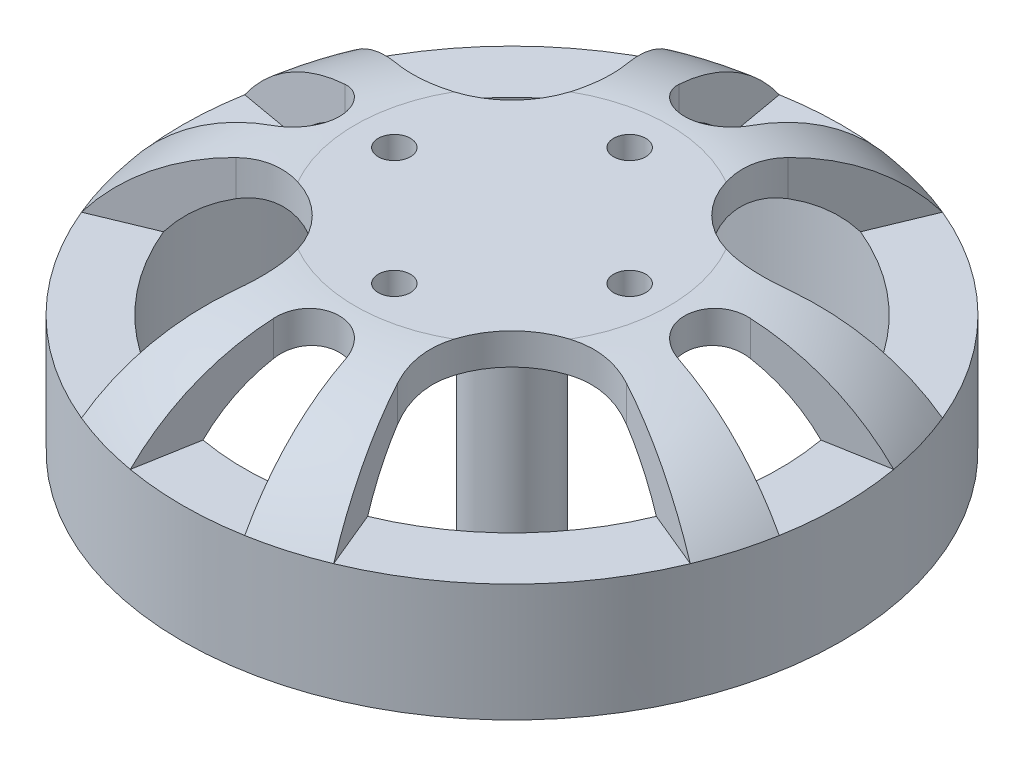
SolidWorks part; units mm, degrees
ref_plane "Front Plane" through (0, 0, 0) normal (0, 0, 1) x (1, 0, 0)
ref_plane "Top Plane" through (0, 0, 0) normal (0, 1, 0) x (1, 0, 0)
ref_plane "Right Plane" through (0, 0, 0) normal (1, 0, 0) x (0, 0, -1)
sketch "Sketch2" plane through (0, 0, 0) normal (0, 0, 1) x (1, 0, 0)
  line L0 (0, 0) -> (0, 19)
  line L1 (-21, 13.5) -> (-21, 6)
  line L2 (0, 19) -> (-10, 19)
  line L3 (0, 9.5) -> (-21, 9.5) construction
  line L4 (-21, 6) -> (-17, 6)
  line L5 (-17, 6) -> (-17, 13.5)
  line L6 (0, 0) -> (-2.5, 0)
  line L7 (-2.5, 0) -> (-2.5, 17)
  line L8 (-2.5, 17) -> (-10, 17)
  arc A0 (-10, 19) -> (-21, 13.5) centre (-10, 5.25) ccw
  arc A1 (-10, 17) -> (-17, 13.5) centre (-10, 8.25) ccw
  dimension "D1" = 21
  dimension "D2" = 19
  dimension "D3" = 7.5
  dimension "D4" = 10
  dimension "D5" = 4
  dimension "D6" = 2.5
  dimension "D7" = 2
  dimension "D8" = 4
revolve "Revolve2" add sketch "Sketch2" angle 360 about L0
hole_wizard "M2.5x0.45 Tapped Hole1" positions "Sketch4" profile "Sketch3" tap size "M2.5x0.45" standard "ANSI Metric" end condition up to next
sketch "Sketch4" plane through (0, 19, 0) normal (0, 1, 0) x (1, 0, 0)
  line L0 (0, 7.5) -> (0, -7.5) construction
  line L3 (-7.5, 0) -> (7.5, 0) construction
  point P0 (7.5, 0)
  point P2 (0, 7.5)
  point P4 (-7.5, 0)
  point P6 (0, -7.5)
  dimension "D1" = 15
sketch "Sketch3" plane through (7.5, 19, 0) normal (1, 0, 0) x (0, 0, 1)
  line L0 (0, 0) -> (0, 2)
  line L1 (0, 2) -> (1.025, 2)
  line L2 (1.025, 2) -> (1.025, 0)
  line L5 (1.025, 0) -> (0, 0)
  line L11 (0, -6.35) -> (0, 107.95) construction
  dimension "Thread Major Dia." = 2.05
  dimension "Thru Tap Drill Depth" = 2
sketch "Sketch6" plane through (0, 19, 0) normal (0, 1, 0) x (1, 0, 0)
  line L0 (0, 0) -> (21, 0) construction
  line L1 (0, 0) -> (0, 21) construction
  line L2 (12.9101, 2.2764) -> (20.681, 3.6466)
  line L3 (12.9101, -2.2764) -> (20.681, -3.6466)
  line L4 (0, 0) -> (14.8492, 14.8492) construction
  line L5 (8.0364, 19.4015) -> (5.1545, 12.4442)
  line L6 (19.4015, 8.0364) -> (12.4442, 5.1545)
  circle A0 centre (0, 0) radius 21 construction
  arc A1 (12.9101, 2.2764) -> (12.9101, -2.2764) centre (13.3115, 0) ccw
  arc A2 (20.681, 3.6466) -> (20.681, -3.6466) centre (0, 0) cw
  arc A3 (5.1545, 12.4442) -> (12.4442, 5.1545) centre (10.3091, 10.3091) ccw
  arc A4 (8.0364, 19.4015) -> (19.4015, 8.0364) centre (0, 0) cw
  point P11 (11, 0)
  point P18 (6.364, 6.364)
  dimension "D1" = 11
  dimension "D2" = 20
  dimension "D3" = 45
  dimension "D4" = 9
  dimension "D5" = 45
extrude "Cut-Extrude1" cut sketch "Sketch6" against normal blind 5.5
pattern_circular "CirPattern1" count 4 over 360 about axis through (0, 13.5, 0) along (0, -1, 0) of "Cut-Extrude1"
